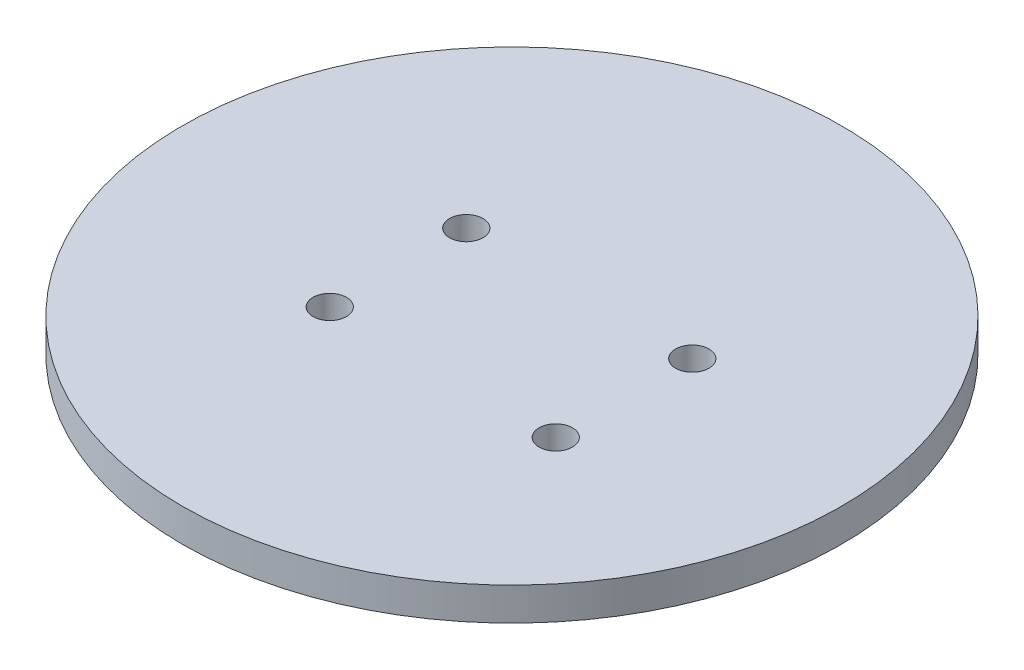
SolidWorks part; units mm, degrees
ref_plane "Front Plane" through (0, 0, 0) normal (0, 0, 1) x (1, 0, 0)
ref_plane "Top Plane" through (0, 0, 0) normal (0, 1, 0) x (1, 0, 0)
ref_plane "Right Plane" through (0, 0, 0) normal (1, 0, 0) x (0, 0, -1)
sketch "Sketch2" plane through (0, 0, 0) normal (0, 1, 0) x (1, 0, 0)
  circle A0 centre (0, 0) radius 35
  dimension "D1" = 70
extrude "Boss-Extrude1" add sketch "Sketch2" along normal blind 3.5
ref_plane "Plane1" through (-4, 0, 0) normal (1, 0, 0) x (0, 0, -1)
sketch "Sketch33" plane through (0, 0, 0) normal (0, -1, 0) x (1, 0, 0)
  circle A0 centre (0, 0) radius 30
  dimension "D1" = 60
extrude "Boss-Extrude3" add sketch "Sketch33" along normal blind 2.2
ref_plane "Plane2" through (0, -4.2, 0) normal (0, -1, 0) x (-1, 0, 0)
sketch "Sketch35" plane through (64.9204, -4.2, -6.6124) normal (0, 1, 0) x (1, 0, 0)
  line L0 (-64.9204, 23.3876) -> (-64.9204, -51.1324) construction
  line L1 (-64.9204, -6.5857) -> (-104.2271, -6.5857) construction
  line L3 (-62.0204, -8.2857) -> (-67.8204, -8.2857)
  line L4 (-62.0204, -8.2857) -> (-62.0204, -4.8857)
  line L5 (-62.0204, -4.8857) -> (-67.8204, -4.8857)
  line L6 (-67.8204, -8.2857) -> (-67.8204, -4.8857)
  circle A0 centre (-64.9204, -6.6124) radius 30 construction
  circle A1 centre (-64.9204, -6.6124) radius 30 construction
  dimension "D1" = 3.4
  dimension "D2" = 5.8
  dimension "D3" = 1.7
  dimension "D4" = 2.9
extrude "Boss-Extrude4" add sketch "Sketch35" against normal blind 6
shell "Shell2" thickness 1 removed face at (0, -10.2, -0.0268) outward yes
sketch "Sketch39" plane through (0, -2.2, 0) normal (0, -1, 0) x (-1, 0, 0)
  circle A0 centre (0, 0) radius 4.25
  circle A1 centre (0, 0) radius 5.5
extrude "Boss-Extrude5" add sketch "Sketch39" along normal blind 9
sketch "Sketch41" plane through (0, -10.2, 0) normal (0, -1, 0) x (-1, 0, 0)
  line L0 (0, 1.7268) -> (0, -7.344) construction
  line L1 (-2.9, 1.7268) -> (2.9, 1.7268) construction
  circle A0 centre (0, 0) radius 3.7
  circle A1 centre (0, 0) radius 4.5
extrude "Boss-Extrude6" add sketch "Sketch41" along normal blind 4
sketch "Sketch42" plane through (0, 3.5, 0) normal (0, 1, 0) x (1, 0, 0)
  circle A0 centre (-10.5052, 5.6583) radius 1.775
  circle A1 centre (13.4948, 5.6583) radius 1.775
  circle A2 centre (13.4948, -8.8417) radius 1.775
  circle A3 centre (-10.5052, -8.8417) radius 1.775
  dimension "D1" = 2
  dimension "D2" = 2
extrude "Cut-Extrude1" cut sketch "Sketch42" against normal up to surface (5.7 mm away) up to face at (0, -2.2, -30)
